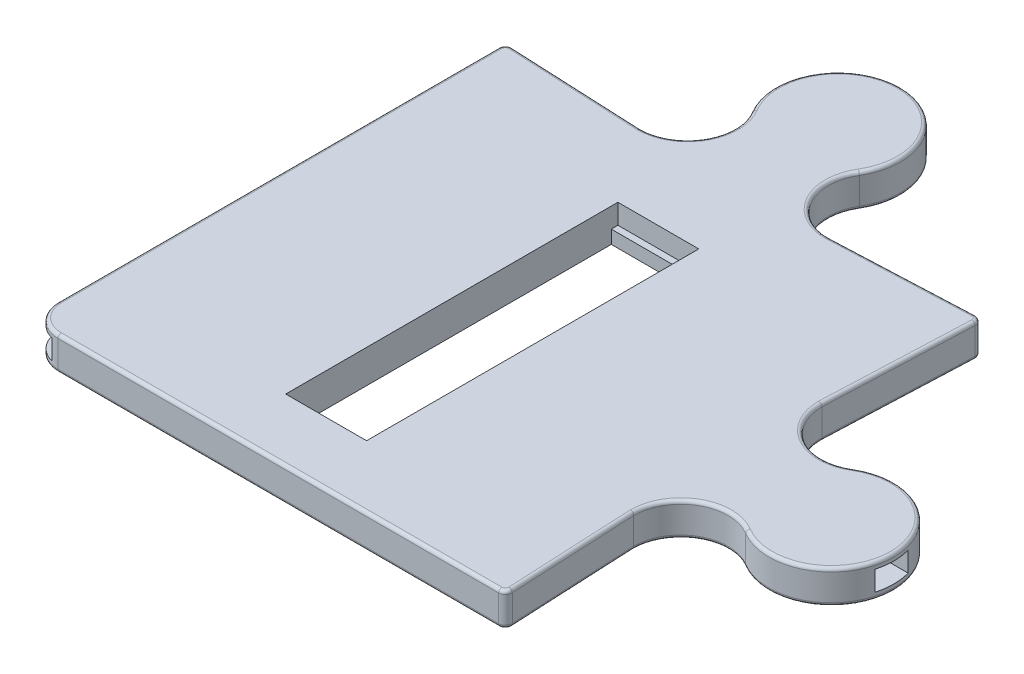
SolidWorks part; units mm, degrees
ref_plane "Front Plane" through (0, 0, 0) normal (0, 0, 1) x (1, 0, 0)
ref_plane "Top Plane" through (0, 0, 0) normal (0, 1, 0) x (1, 0, 0)
ref_plane "Right Plane" through (0, 0, 0) normal (1, 0, 0) x (0, 0, -1)
sketch "Sketch1" plane through (0, 0, 0) normal (0, 1, 0) x (1, 0, 0)
  line L0 (-31, -36) -> (37, -36) construction
  line L1 (-36, 37) -> (-36, -31) construction
  line L2 (-14.1421, 36) -> (-36, 37) construction
  line L3 (37, 37) -> (14.1421, 36) construction
  line L4 (36, 13.1421) -> (37, 37) construction
  line L5 (37, -36) -> (36, -15.1421) construction
  line L6 (-35.4, 36.3719) -> (-35.4, -31)
  line L7 (-36, 36) -> (36, 36) construction
  line L8 (-36, 36) -> (-36, -36) construction
  line L9 (-36, -36) -> (36, -36) construction
  line L10 (36, 36) -> (36, -36) construction
  line L11 (-31, -35.4) -> (36.3705, -35.4)
  line L12 (36.3705, -35.4) -> (35.4, -15.1568)
  line L13 (35.4, 13.155) -> (36.3732, 36.372)
  line L14 (36.3732, 36.372) -> (14.1555, 35.4)
  line L15 (-14.1562, 35.4) -> (-35.4, 36.3719)
  line L16 (-30, -24) -> (30, -24) construction
  line L17 (-30, 29) -> (30, 29) construction
  line L18 (-30, 29) -> (-30, -31) construction
  line L19 (-30, -31) -> (30, -31) construction
  line L20 (30, 29) -> (30, -31) construction
  line L21 (-30, 24) -> (30, 24) construction
  line L22 (-30, 24) -> (-30, -26) construction
  line L23 (-30, -26) -> (30, -26) construction
  line L24 (30, 24) -> (30, -26) construction
  arc A0 (-36, -31) -> (-31, -36) centre (-31, -31) ccw construction
  arc A1 (-14.1421, 36) -> (-8.571, 45.8485) centre (-14.1421, 42.5) ccw construction
  arc A2 (8.571, 45.8485) -> (-8.571, 45.8485) centre (0, 51) ccw construction
  arc A3 (8.571, 45.8485) -> (14.1421, 36) centre (14.1421, 42.5) ccw construction
  arc A4 (36, 13.1421) -> (45.8485, 7.571) centre (42.5, 13.1421) ccw construction
  arc A5 (45.8485, -9.571) -> (45.8485, 7.571) centre (51, -1) ccw construction
  arc A6 (45.8485, -9.571) -> (36, -15.1421) centre (42.5, -15.1421) ccw construction
  arc A7 (-35.4, -31) -> (-31, -35.4) centre (-31, -31) ccw
  arc A8 (46.1576, -9.0567) -> (35.4, -15.1568) centre (42.5, -15.1421) ccw
  arc A9 (46.1576, -9.0567) -> (46.1576, 7.0567) centre (51, -1) ccw
  arc A10 (35.4, 13.155) -> (46.1576, 7.0567) centre (42.5, 13.1421) ccw
  arc A11 (8.0567, 46.1576) -> (14.1555, 35.4) centre (14.1421, 42.5) ccw
  arc A12 (8.0567, 46.1576) -> (-8.0567, 46.1576) centre (0, 51) ccw
  arc A13 (-14.1562, 35.4) -> (-8.0567, 46.1576) centre (-14.1421, 42.5) ccw
  point P32 (36, 0)
  point P34 (0, 36)
  dimension "D5" = 6.5
  dimension "D6" = 10
  dimension "D7" = 6.5
  dimension "D13" = 5
  dimension "D9" = 10
  dimension "D11" = 6.5
  dimension "D12" = 6.5
  dimension "D1" = 72
  dimension "D2" = 1
  dimension "D3" = 1
  dimension "D4" = 15
  dimension "D8" = 1
  dimension "D10" = 35
  dimension "D14" = 15
  dimension "D15" = 36
  dimension "D16" = 1
  dimension "D18" = 60
  dimension "D19" = 60
  dimension "D20" = 5
  dimension "D21" = 6
  dimension "D22" = 5
  dimension "D23" = 50
  dimension "D24" = 2
  dimension "D17" = 0.6
extrude "Boss-Extrude1" add sketch "Sketch1" along normal blind 5
sketch "Sketch6" plane through (0, 0, 0) normal (0, -1, 0) x (1, 0, 0)
  line L0 (-35.4, -36.3719) -> (-35.4, 31) construction
  line L1 (-35.4, 17.9) -> (-27.4, 17.9)
  line L2 (-35.4, 17.9) -> (-35.4, -16.1)
  line L3 (-35.4, -16.1) -> (-27.4, -16.1)
  line L4 (-27.4, 17.9) -> (-27.4, -16.1)
  line L5 (-31, 35.4) -> (36.3705, 35.4) construction
  line L6 (-35.4, 14.65) -> (-30.4, 14.65)
  line L7 (-35.4, 14.65) -> (-35.4, -12.85)
  line L8 (-35.4, -12.85) -> (-30.4, -12.85)
  line L9 (-30.4, 14.65) -> (-30.4, -12.85)
  point P15 (-27.4, 0.9)
  point P16 (-30.4, 0.9)
  line M28 (-35.4, 31) -> (-35.4, -36.3719)
  dimension "D1" = 8
  dimension "D2" = 20.75
  dimension "D3" = 27.5
  dimension "D4" = 5
  dimension "D5" = 34
extrude "Cut-Extrude3" cut sketch "Sketch6" against normal blind 3 from offset 1 contours L6 L9 L8 L3 L4 L1 M28 | L9 L6 L2 L8 region at (-29.8665, 0, 0.9) region at (-32.9, 0, 0.9) offset against normal yes
extrude "Cut-Extrude4" cut sketch "Sketch6<3>" against normal up to next contours L9 L6 L2 L8 region at (-32.9, 0, 0.9)
sketch "Sketch6<3>" plane through (0, 0, 0) normal (0, -1, 0) x (1, 0, 0) same geometry as "Sketch6"
sketch "Sketch8" plane through (0, 0, 0) normal (0, -1, 0) x (1, 0, 0)
  line L1 (-2.5, -51.4) -> (2.5, -51.4)
  line L2 (-2.5, -51.4) -> (-2.5, -60.4)
  line L3 (-2.5, -60.4) -> (2.5, -60.4)
  line L4 (2.5, -51.4) -> (2.5, -60.4)
  line L5 (51.4, 3.5) -> (60.4, 3.5)
  line L6 (51.4, 3.5) -> (51.4, -1.5)
  line L7 (51.4, -1.5) -> (60.4, -1.5)
  line L8 (60.4, 3.5) -> (60.4, -1.5)
  arc A0 (-8.0567, -46.1576) -> (8.0567, -46.1576) centre (0, -51) ccw construction
  arc A1 (46.1576, -7.0567) -> (46.1576, 9.0567) centre (51, 1) ccw construction
  point P4 (0, -60.4)
  point P13 (60.4, 1)
  dimension "D1" = 5
  dimension "D2" = 9
  dimension "D3" = 5
  dimension "D4" = 9
extrude "Cut-Extrude5" cut sketch "Sketch8" against normal blind 3 from offset 1 offset against normal yes
sketch "Sketch9" plane through (0, 0, 0) normal (0, -1, 0) x (1, 0, 0)
  line L0 (-31, 35.4) -> (36.3705, 35.4) construction
  line L1 (-35.4, 14.65) -> (-35.4, 31) construction
  line L2 (-31.7636, 35.3332) -> (-35.4, 31) construction
  line L3 (-33.2571, 29.735) -> (-30.0429, 33.565) construction
  line L4 (-30.0429, 33.565) -> (-33.2571, 29.735) construction
  line L5 (-30.0429, 33.565) -> (-32.7119, 35.8048)
  line L6 (-33.2571, 29.735) -> (-35.926, 31.9747)
  line L7 (-32.7119, 35.8048) -> (-35.926, 31.9747)
  circle A0 centre (-31.65, 31.65) radius 2.5
  arc A1 (-31, 35.4) -> (-35.4, 31) centre (-31, 31) ccw construction
  arc M41 (-31, 35.4) -> (-35.4, 31) centre (-31, 31) ccw
  dimension "D1" = 5
  dimension "D3" = 3.75
  dimension "D4" = 5.6569
  dimension "D2" = 3.75
extrude "Cut-Extrude6" cut sketch "Sketch9" against normal blind 3 from offset 1 contours A0 L5 L6 M41 | A0 L5 region at (-33.6239, 0, 33.3064) region at (-31.65, 0, 31.65) offset against normal yes
sketch "Sketch11" plane through (-35.4, 0, 0) normal (-1, 0, 0) x (0, 0, 1)
  line L0 (-13.155, 0) -> (-36.372, 0) construction
  line L1 (-25.1, 3) -> (-19.1, 3)
  line L2 (-25.1, 3) -> (-25.1, 1.5)
  line L3 (-25.1, 1.5) -> (-19.1, 1.5)
  line L4 (-19.1, 3) -> (-19.1, 1.5)
  line L5 (-16.1, 4) -> (-16.1, 1) construction
  line L6 (35.4, 0) -> (15.1568, 0) construction
  line L7 (20.9, 3) -> (26.9, 3)
  line L8 (20.9, 3) -> (20.9, 1.5)
  line L9 (20.9, 1.5) -> (26.9, 1.5)
  line L10 (26.9, 3) -> (26.9, 1.5)
  line L12 (17.9, 4) -> (17.9, 1) construction
  dimension "D1" = 3
  dimension "D2" = 1.5
  dimension "D3" = 3
  dimension "D4" = 6
  dimension "D5" = 3
  dimension "D6" = 1.5
  dimension "D7" = 6
  dimension "D8" = 3
fillet "Fillet1" radius 0.5 17 edges at (-35.4, 0, 22.825) (-34.1113, 0, 34.1113) (2.6853, 0, 35.4) (35.8853, 0, 25.2784) (38.9978, 0, 8.966) (60.4, 0, 1) (38.9986, 0, -6.9655) (35.8866, 0, -24.7635) (25.2643, 0, -35.886) (7.9657, 0, -38.9984) (0, 0, -60.4) (-7.9658, 0, -38.9981) (-24.7781, 0, -35.886) (-35.4, 0, -24.611) (-32.9, 0, -12.85) (-30.4, 0, 0.9) (-32.9, 0, 14.65)
fillet "Fillet2" radius 0.5 13 edges at (-7.9658, 5, -38.9981) (0, 5, -60.4) (7.9657, 5, -38.9984) (25.2643, 5, -35.886) (35.8866, 5, -24.7635) (38.9986, 5, -6.9655) (60.4, 5, 1) (38.9978, 5, 8.966) (35.8853, 5, 25.2784) (2.6853, 5, 35.4) (-34.1113, 5, 34.1113) (-35.4, 5, -2.686) (-24.7781, 5, -35.886)
fillet "Fillet3" radius 1 9 edges at (36.2202, 0.1464, -36.2187) (36.2202, 4.8536, -36.2187) (36.3732, 2.5, -36.372) (-35.2536, 0.1464, -36.2186) (-35.2536, 4.8536, -36.2186) (36.2169, 0.1464, 35.2536) (36.2169, 4.8536, 35.2536) (36.3705, 2.5, 35.4) (-35.4, 2.5, -36.3719)
extrude "Cut-Extrude9" cut sketch "Sketch11" against normal blind 3
chamfer "Chamfer1" distance 1 angle 50 2 edges at (-35.4, 1.5, 23.9) (-35.4, 1.5, -22.1) first distance on face at (-35.4, 2.25, -22.1)
sketch "Sketch12" plane through (0, 5, 0) normal (0, 1, 0) x (1, 0, 0)
  text T0 "I" font "Poppins" height 50
extrude "Cut-Extrude10" cut sketch "Sketch12" against normal through all
sketch "Sketch13" plane through (0, 0, 0) normal (0, -1, 0) x (1, 0, 0)
  line L0 (6.0387, -24) -> (6.0387, 26) construction
  line L1 (-6.1315, 26) -> (6.0387, 26)
  line L2 (-6.1315, 26) -> (-6.1315, 25)
  line L3 (-6.1315, 25) -> (6.0387, 25)
  line L4 (6.0387, 26) -> (6.0387, 25)
  line L5 (-6.1315, 26) -> (-6.1315, -24) construction
  line L6 (6.0387, -24) -> (-6.1315, -24)
  line L7 (6.0387, -24) -> (6.0387, -23)
  line L8 (6.0387, -23) -> (-6.1315, -23)
  line L9 (-6.1315, -24) -> (-6.1315, -23)
  dimension "D1" = 1
  dimension "D2" = 1
extrude "Boss-Extrude2" add sketch "Sketch13" against normal blind 2
